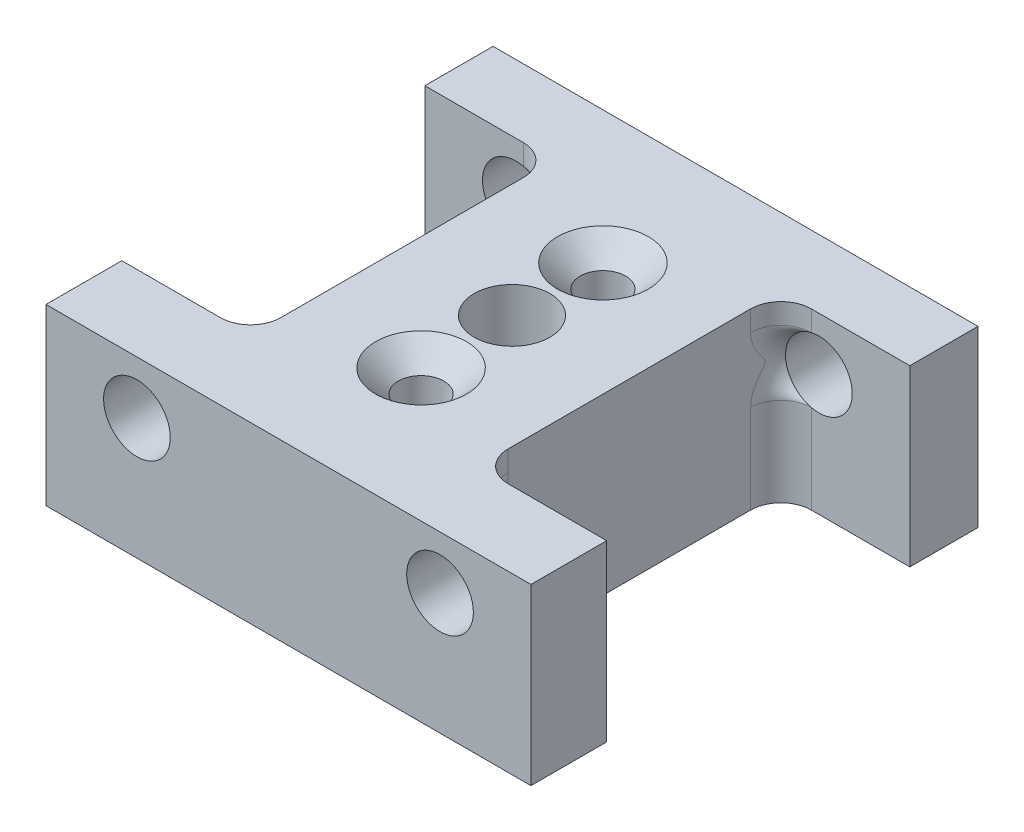
SolidWorks part; units mm, degrees
ref_plane "前视基准面" through (0, 0, 0) normal (0, 0, 1) x (1, 0, 0)
ref_plane "上视基准面" through (0, 0, 0) normal (0, 1, 0) x (1, 0, 0)
ref_plane "右视基准面" through (0, 0, 0) normal (1, 0, 0) x (0, 0, -1)
sketch "草图1" plane through (0, 0, 0) normal (0, 0, 1) x (1, 0, 0)
  line L0 (163, -49.74) -> (-23.7584, -49.74) construction
  line L1 (2, -49.74) -> (34, -49.74)
  line L2 (2, -49.74) -> (2, -38.24)
  line L3 (2, -38.24) -> (34, -38.24)
  line L4 (34, -49.74) -> (34, -38.24)
  circle A0 centre (8, -41.74) radius 2.2
  circle A1 centre (28, -41.7379) radius 2.2
  dimension "D1" = 6
  dimension "D4" = 4.4
  dimension "D5" = 4.4
  dimension "D2" = 6
  dimension "D3" = 3.5
extrude "凸台-拉伸1" add sketch "草图1" along normal blind 29.5
sketch "草图2" plane through (0, -49.74, 0) normal (0, -1, 0) x (1, 0, 0)
  line L0 (2, 29.5) -> (34, 0) construction
  line L1 (34, 29.5) -> (2, 0) construction
  circle A0 centre (18, 14.75) radius 2.5
  dimension "D1" = 5
extrude "切除-拉伸1" cut sketch "草图2" against normal blind 29.5
sketch "草图3" plane through (0, -49.74, 0) normal (0, -1, 0) x (1, 0, 0)
  line L0 (18, 0) -> (18, 29.5) construction
  line L1 (2, 0) -> (34, 0) construction
  line L2 (2, 29.5) -> (34, 29.5) construction
  circle A0 centre (18, 8.75) radius 1.5
  circle A1 centre (18, 20.75) radius 1.5
  dimension "D1" = 12
  dimension "D2" = 8.75
  dimension "D3" = 3
  dimension "D4" = 3
extrude "切除-拉伸2" cut sketch "草图3" against normal blind 29.5
chamfer "倒角1" distance 1.5 angle 45 2 edges at (18, -38.24, 7.25) (18, -38.24, 19.25)
sketch "草图4" plane through (0, -38.24, 0) normal (0, 1, 0) x (1, 0, 0)
  line L0 (2, -29.5) -> (2, 0) construction
  line L1 (2, -4.5) -> (10.5, -4.5)
  line L2 (2, -4.5) -> (2, -24.5)
  line L3 (2, -24.5) -> (10.5, -24.5)
  line L4 (34, -4.5) -> (34, -24.5)
  line L5 (34, -29.5) -> (34, 0) construction
  line L6 (34, 0) -> (2, 0) construction
  line L8 (10.5, -4.5) -> (10.5, -24.5)
  line L10 (25.5, -4.5) -> (25.5, -24.5)
  line L11 (25.5, -4.5) -> (34, -4.5)
  line L12 (25.5, -24.5) -> (34, -24.5)
  dimension "D1" = 20
  dimension "D2" = 4.5
  dimension "D3" = 15
  dimension "D4" = 8.5
extrude "切除-拉伸3" cut sketch "草图4" against normal blind 20
fillet "圆角1" radius 2 4 edges at (25.5, -43.99, 24.5) (10.5, -43.99, 24.5) (10.5, -43.99, 4.5) (25.5, -43.99, 4.5)
